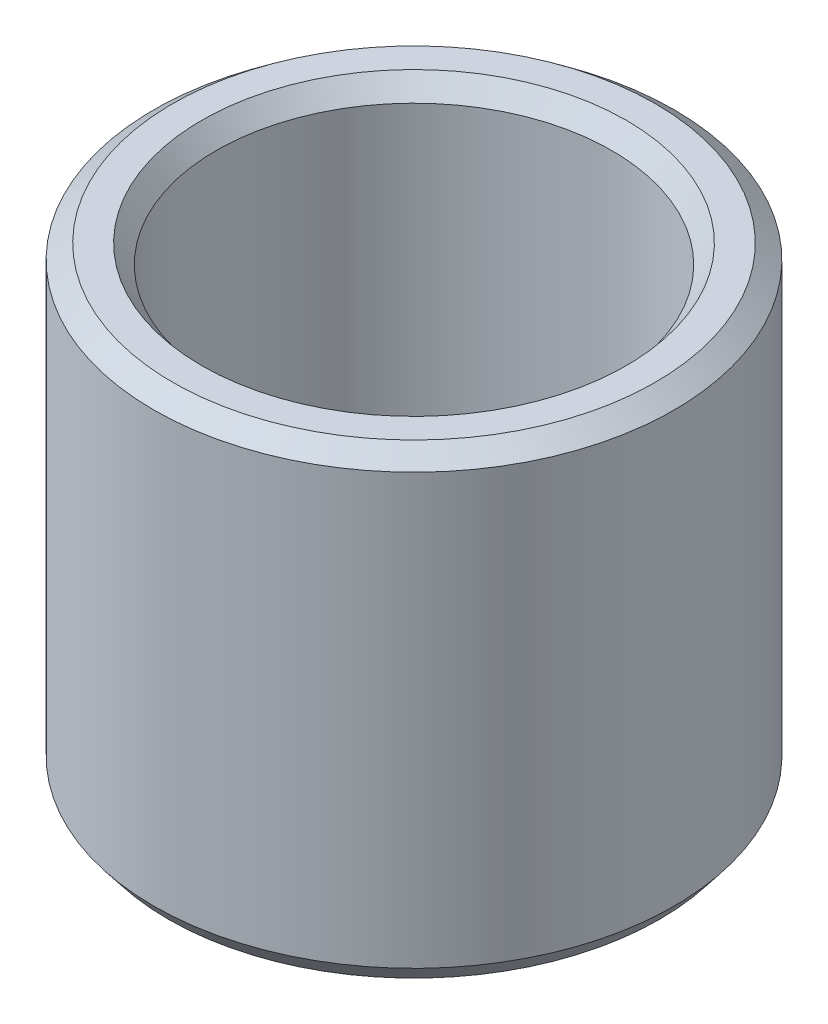
SolidWorks part; units mm, degrees
ref_plane "Front Plane" through (0, 0, 0) normal (0, 0, 1) x (1, 0, 0)
ref_plane "Top Plane" through (0, 0, 0) normal (0, 1, 0) x (1, 0, 0)
ref_plane "Right Plane" through (0, 0, 0) normal (1, 0, 0) x (0, 0, -1)
sketch "Sketch1" plane through (0, 0, 0) normal (0, 1, 0) x (1, 0, 0)
  circle A0 centre (0, 0) radius 42.5
  dimension "SLEEVE_OD" = 85
extrude "Boss-Extrude1" add sketch "Sketch1" along normal blind 75.6518
sketch "Sketch2" plane through (0, 0, 0) normal (0, 1, 0) x (1, 0, 0)
  circle A0 centre (0, 0) radius 32.317
  dimension "BORE_D" = 64.634
extrude "Cut-Extrude1" cut sketch "Sketch2" along normal through all
chamfer "Chamfer1" distance 2.3874 angle 52.127 4 edges at (0, 75.6518, 32.317) (0, 0, 32.317) (0, 0, 42.5) (0, 75.6518, 42.5) first distance on face at (0, 75.6518, 32.317) first distance on face at (0, 0, 32.317) first distance on face at (0, 75.6518, 42.5)
